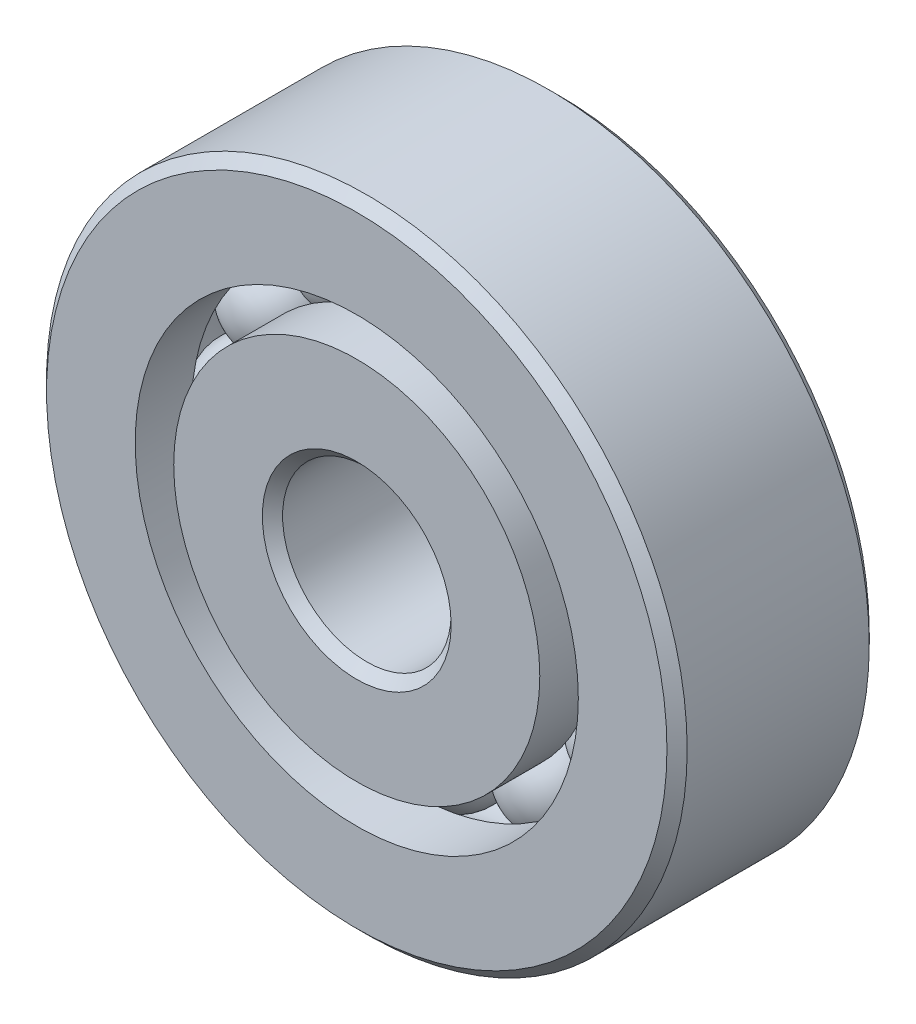
SolidWorks part; units mm, degrees
ref_plane "Front Plane" through (0, 0, 0) normal (0, 0, 1) x (1, 0, 0)
ref_plane "Top Plane" through (0, 0, 0) normal (0, 1, 0) x (1, 0, 0)
ref_plane "Right Plane" through (0, 0, 0) normal (1, 0, 0) x (0, 0, -1)
sketch "Sketch1" plane through (0, 0, 0) normal (1, 0, 0) x (0, 0, -1)
  line L0 (-3, 0) -> (3, 0) construction
  line L1 (0, 9.5) -> (0, -9.5) construction
  line L2 (2.7, 9.5) -> (-2.7, 9.5)
  line L3 (-2.7, 9.5) -> (-3, 9.2)
  line L4 (-3, 9.2) -> (-3, 6.5714)
  line L5 (-3, 6.5714) -> (-1.3333, 6.5714)
  line L6 (3, 6.5714) -> (1.3333, 6.5714)
  line L7 (3, 9.2) -> (3, 6.5714)
  line L8 (2.7, 9.5) -> (3, 9.2)
  line L9 (0, 9.5) -> (0, 6) construction
  line L10 (0, 6) -> (0, 2.5) construction
  arc A0 (-1.3333, 6.5714) -> (1.3333, 6.5714) centre (0, 6) cw
  point P14 (0, 2.5)
  dimension "Width" = 6
  dimension "OD" = 19
  dimension "D1" = 45
  dimension "D2" = 0.3
  dimension "Shaft Dia" = 5
  dimension "D3" = 2.6667
  dimension "D4" = 0.5714
revolve "Revolve1" add sketch "Sketch1" angle 360 about L0
sketch "Sketch3" plane through (0, 0, 0) normal (1, 0, 0) x (0, 0, -1)
  line L0 (-3, 5.4286) -> (-1.3333, 5.4286)
  line L1 (0, 9.5) -> (0, -9.5) construction
  line L2 (-3, 9.2) -> (-3, 6.5714) construction
  line L3 (-3, 5.4286) -> (-3, 2.8)
  line L4 (-2.7, 9.5) -> (-3, 9.2) construction
  line L5 (-3, 2.8) -> (-2.7, 2.5)
  line L6 (-2.7, 2.5) -> (2.7, 2.5)
  line L7 (2.7, 9.5) -> (2.7, -9.5) construction
  line L8 (2.7, 2.5) -> (3, 2.8)
  line L9 (3, -9.2) -> (3, 9.2) construction
  line L10 (3, 2.8) -> (3, 5.4286)
  line L11 (3, 5.4286) -> (1.3333, 5.4286)
  line L13 (2.7, 9.5) -> (3, 9.2) construction
  arc A0 (1.3333, 6.5714) -> (-1.3333, 6.5714) centre (0, 6) ccw construction
  arc A1 (1.3333, 5.4286) -> (-1.3333, 5.4286) centre (0, 6) cw
revolve "Revolve3" add sketch "Sketch3" angle 360 about L0
sketch "Sketch4" plane through (0, 0, 0) normal (1, 0, 0) x (0, 0, -1)
  line L0 (-1.4506, 6) -> (1.4506, 6)
  arc A2 (-1.4506, 6) -> (1.4506, 6) centre (0, 6) cw
  arc A3 (1.3333, 6.5714) -> (-1.3333, 6.5714) centre (0, 6) ccw construction
revolve "Revolve4" add sketch "Sketch4" angle 360 about L0
ref_axis "Axis1" through (0, 0, -3) along (0, 0, 1)
pattern_circular "CirPattern1" count 12 every 30 about axis through (0, 0, -3) along (0, 0, 1) of bodies 104
sketch "Sketch5" plane through (0, 0, 0) normal (1, 0, 0) x (0, 0, -1)
  line L0 (-3, 6.5714) -> (-1.3333, 6.5714) construction
  line L1 (-2.85, 6.5714) -> (-1.4506, 6.5714)
  line L2 (-2.85, 6.5714) -> (-2.85, 5.4286)
  line L3 (-2.85, 5.4286) -> (-1.4506, 5.4286)
  line L4 (-1.4506, 6.5714) -> (-1.4506, 5.4286)
  line L5 (-3, 5.4286) -> (-1.3333, 5.4286) construction
  line L6 (3, 6.5714) -> (1.3333, 6.5714) construction
  line L7 (2.85, 6.5714) -> (1.4506, 6.5714)
  line L8 (2.85, 6.5714) -> (2.85, 5.4286)
  line L9 (2.85, 5.4286) -> (1.4506, 5.4286)
  line L10 (1.4506, 6.5714) -> (1.4506, 5.4286)
  line L11 (3, 5.4286) -> (1.3333, 5.4286) construction
  line L12 (-2.7, 9.5) -> (-3, 9.2) construction
  point P18 (-2.85, 9.35)
ref_axis "Axis2" through (0, 0, -2.7) along (0, 0, 1)
equation "\"D2@Sketch1\" = \"Width@Sketch1\"*.05"
equation "\"D3@Sketch1\" = \"Width@Sketch1\"/2.25"
equation "\"D4@Sketch1\" = (((\"OD@Sketch1\"-\"Width@Sketch1\")/2)/3.25)/3.5"
equation "\"D2@CirPattern1\" = 360/\"Balls@CirPattern1\""
